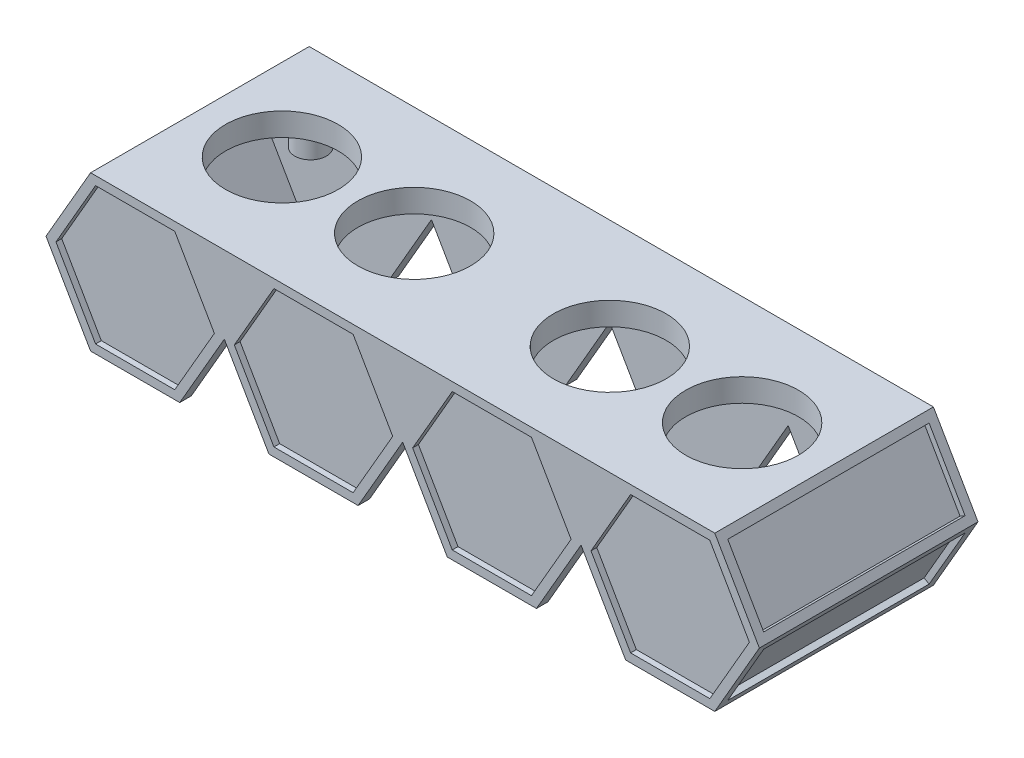
SolidWorks part; units mm, degrees
ref_plane "Front Plane" through (0, 0, 0) normal (0, 0, 1) x (1, 0, 0)
ref_plane "Top Plane" through (0, 0, 0) normal (0, 1, 0) x (1, 0, 0)
ref_plane "Right Plane" through (0, 0, 0) normal (1, 0, 0) x (0, 0, -1)
sketch "Sketch1" plane through (0, 0, 0) normal (0, 0, 1) x (1, 0, 0)
  line L0 (7.75, 13.4234) -> (23.25, 13.4234)
  line L1 (15.5, 0) -> (7.75, 13.4234)
  line L2 (7.75, 13.4234) -> (-7.75, 13.4234)
  line L3 (-7.75, 13.4234) -> (-15.5, 0)
  line L4 (-15.5, 0) -> (-7.75, -13.4234)
  line L5 (-7.75, -13.4234) -> (7.75, -13.4234)
  line L6 (7.75, -13.4234) -> (15.5, 0)
  line L7 (15.5, 0) -> (23.25, -13.4234)
  line L8 (23.25, -13.4234) -> (38.75, -13.4234)
  line L9 (38.75, -13.4234) -> (46.5, 0)
  line L10 (46.5, 0) -> (38.75, 13.4234)
  line L11 (38.75, 13.4234) -> (23.25, 13.4234)
  line L12 (23.25, 13.4234) -> (15.5, 0)
  line L13 (46.5, 0) -> (54.25, -13.4234)
  line L14 (54.25, -13.4234) -> (69.75, -13.4234)
  line L15 (69.75, -13.4234) -> (77.5, 0)
  line L16 (77.5, 0) -> (69.75, 13.4234)
  line L17 (69.75, 13.4234) -> (54.25, 13.4234)
  line L18 (54.25, 13.4234) -> (46.5, 0)
  line L19 (77.5, 0) -> (85.25, -13.4234)
  line L20 (85.25, -13.4234) -> (100.75, -13.4234)
  line L21 (100.75, -13.4234) -> (108.5, 0)
  line L22 (108.5, 0) -> (100.75, 13.4234)
  line L23 (100.75, 13.4234) -> (85.25, 13.4234)
  line L24 (85.25, 13.4234) -> (77.5, 0)
  line L25 (38.75, 13.4234) -> (54.25, 13.4234)
  line L26 (69.75, 13.4234) -> (85.25, 13.4234)
  circle A0 centre (0, 0) radius 13.4234 construction
  circle A1 centre (31, 0) radius 13.4234 construction
  circle A2 centre (62, 0) radius 13.4234 construction
  circle A3 centre (93, 0) radius 13.4234 construction
  dimension "D1" = 31
extrude "Boss-Extrude1" add sketch "Sketch1" along normal blind 38 contours L5 L6 L1 L2 L3 L4 | L12 L0 L1 | L11 L12 L7 L8 L9 L10 | L25 L10 L18 | L17 L18 L13 L14 L15 L16 | L26 L16 L24 | L23 L24 L19 L20 L21 L22 region at (15.5, 8.9489, 0) region at (0, 0, 0) region at (31, 0, 0) region at (46.5, 8.9489, 0) region at (62, 0, 0) region at (77.5, 8.9489, 0) region at (93, 0, 0)
ref_plane "Plane1" through (0, 0, 19) normal (0, 0, 1) x (1, 0, 0)
shell "Shell2" thickness 2 removed face at (0, -13.4234, 19) removed face at (11.625, -6.7117, 19) removed face at (19.375, -6.7117, 19) removed face at (31, -13.4234, 19) removed face at (42.625, -6.7117, 19) removed face at (50.375, -6.7117, 19) removed face at (62, -13.4234, 19) removed face at (73.625, -6.7117, 19) removed face at (81.375, -6.7117, 19) removed face at (93, -13.4234, 19)
sketch "Sketch3" plane through (0, 0, 38) normal (0, 0, 1) x (1, 0, 0)
  line L0 (7.75, -13.4234) -> (15.5, 0) construction
  line L1 (13.7679, 0) -> (6.884, 11.9234)
  line L2 (6.884, 11.9234) -> (-6.884, 11.9234)
  line L3 (-6.884, 11.9234) -> (-13.7679, 0)
  line L4 (-13.7679, 0) -> (-6.884, -11.9234)
  line L5 (-6.884, -11.9234) -> (6.884, -11.9234)
  line L6 (6.884, -11.9234) -> (13.7679, 0)
  line L7 (38.75, -13.4234) -> (46.5, 0) construction
  line L8 (44.7679, 0) -> (37.884, 11.9234)
  line L9 (37.884, 11.9234) -> (24.116, 11.9234)
  line L10 (24.116, 11.9234) -> (17.2321, 0)
  line L11 (17.2321, 0) -> (24.116, -11.9234)
  line L12 (24.116, -11.9234) -> (37.884, -11.9234)
  line L13 (37.884, -11.9234) -> (44.7679, 0)
  line L14 (75.7679, 0) -> (68.884, 11.9234)
  line L15 (68.884, 11.9234) -> (55.116, 11.9234)
  line L16 (55.116, 11.9234) -> (48.2321, 0)
  line L17 (48.2321, 0) -> (55.116, -11.9234)
  line L18 (55.116, -11.9234) -> (68.884, -11.9234)
  line L19 (68.884, -11.9234) -> (75.7679, 0)
  line L20 (106.7679, 0) -> (99.884, 11.9234)
  line L21 (99.884, 11.9234) -> (86.116, 11.9234)
  line L22 (86.116, 11.9234) -> (79.2321, 0)
  line L23 (79.2321, 0) -> (86.116, -11.9234)
  line L24 (86.116, -11.9234) -> (99.884, -11.9234)
  line L25 (99.884, -11.9234) -> (106.7679, 0)
  line L26 (69.75, -13.4234) -> (77.5, 0) construction
  line L27 (100.75, -13.4234) -> (108.5, 0) construction
  circle A0 centre (0, 0) radius 11.9234 construction
  circle A1 centre (31, 0) radius 11.9234 construction
  circle A2 centre (62, 0) radius 11.9234 construction
  circle A3 centre (93, 0) radius 11.9234 construction
  dimension "D1" = 1.5
  dimension "D2" = 1.5
  dimension "D3" = 1.5
  dimension "D4" = 1.5
extrude "Cut-Extrude2" cut sketch "Sketch3" against normal blind 1
extrude "Cut-Extrude3" cut sketch "Sketch3<2>" along normal blind 1 from surface starting at face at (46.5, -5.3694, 0)
sketch "Sketch3<2>" plane through (0, 0, 38) normal (0, 0, 1) x (1, 0, 0) same geometry as "Sketch3"
sketch "Sketch4" plane through (81.375, 46.9819, 0) normal (0.866, 0.5, 0) x (0, 0, -1)
  line L8 (-1.5, -52.75) -> (-1.5, -40.25)
  line L9 (-1.5, -40.25) -> (-36.5, -40.25)
  line L10 (-36.5, -40.25) -> (-36.5, -52.75)
  line L11 (-36.5, -52.75) -> (-1.5, -52.75)
  line L12 (-1.5, -52.75) -> (-1.5, -40.25)
  line L13 (-1.5, -40.25) -> (-36.5, -40.25)
  line L14 (-36.5, -40.25) -> (-36.5, -52.75)
  line L15 (-36.5, -52.75) -> (-1.5, -52.75)
  dimension "D1" = 1.5
extrude "Cut-Extrude4" cut sketch "Sketch4" against normal blind 1
sketch "Sketch5" plane through (-11.625, 6.7117, 0) normal (-0.866, 0.5, 0) x (0, 0, 1)
  line L8 (1.5, 6.25) -> (1.5, -6.25)
  line L9 (1.5, -6.25) -> (36.5, -6.25)
  line L10 (36.5, -6.25) -> (36.5, 6.25)
  line L11 (36.5, 6.25) -> (1.5, 6.25)
  line L12 (1.5, 6.25) -> (1.5, -6.25)
  line L13 (1.5, -6.25) -> (36.5, -6.25)
  line L14 (36.5, -6.25) -> (36.5, 6.25)
  line L15 (36.5, 6.25) -> (1.5, 6.25)
  dimension "D1" = 1.5
extrude "Cut-Extrude5" cut sketch "Sketch5" against normal blind 1
sketch "Sketch7" plane through (-11.625, -6.7117, 0) normal (-0.866, -0.5, 0) x (0, 0, 1)
  line L8 (1.5, 6.25) -> (1.5, -6.25)
  line L9 (1.5, -6.25) -> (36.5, -6.25)
  line L10 (36.5, -6.25) -> (36.5, 6.25)
  line L11 (36.5, 6.25) -> (1.5, 6.25)
  line L12 (1.5, 6.25) -> (1.5, -6.25)
  line L13 (1.5, -6.25) -> (36.5, -6.25)
  line L14 (36.5, -6.25) -> (36.5, 6.25)
  line L15 (36.5, 6.25) -> (1.5, 6.25)
  dimension "D1" = 1.5
extrude "Cut-Extrude7" cut sketch "Sketch7" against normal blind 1
sketch "Sketch8" plane through (81.375, -46.9819, 0) normal (0.866, -0.5, 0) x (0, 0, -1)
  line L8 (-1.5, 40.25) -> (-1.5, 52.75)
  line L9 (-1.5, 52.75) -> (-36.5, 52.75)
  line L10 (-36.5, 52.75) -> (-36.5, 40.25)
  line L11 (-36.5, 40.25) -> (-1.5, 40.25)
  line L12 (-1.5, 40.25) -> (-1.5, 52.75)
  line L13 (-1.5, 52.75) -> (-36.5, 52.75)
  line L14 (-36.5, 52.75) -> (-36.5, 40.25)
  line L15 (-36.5, 40.25) -> (-1.5, 40.25)
  dimension "D1" = 1.5
extrude "Cut-Extrude8" cut sketch "Sketch8" against normal blind 1
sketch "Sketch6" plane through (0, 13.4234, 0) normal (0, 1, 0) x (1, 0, 0)
  line L0 (-7.75, -19) -> (100.75, -19) construction
  line L1 (-7.75, -38) -> (-7.75, 0) construction
  line L2 (100.75, -38) -> (100.75, 0) construction
  line L3 (100.75, 0) -> (-7.75, 0) construction
  circle A0 centre (6.5, -19) radius 9.8
  circle A1 centre (29.5, -19) radius 9.8
  circle A2 centre (63.5, -19) radius 9.8
  circle A3 centre (86.5, -19) radius 9.8
  point P21 (46.5, 0)
  dimension "D1" = 19.6
  dimension "D2" = 23
  dimension "D3" = 23
  dimension "D4" = 34
  dimension "D5" = 17
extrude "Cut-Extrude6" cut sketch "Sketch6" against normal blind 10
sketch "Sketch9" plane through (0, 11.4234, 0) normal (0, -1, 0) x (1, 0, 0)
  line L0 (-0.5, 31) -> (-0.5, 7) construction
  line L1 (-0.5, 7) -> (93.5, 7) construction
  line L2 (93.5, 7) -> (93.5, 31) construction
  line L3 (-15.5, 38) -> (-15.5, 0) construction
  line L4 (100.75, 0) -> (-7.75, 0) construction
  circle A0 centre (-0.5, 31) radius 1.5
  circle A1 centre (-0.5, 7) radius 1.5
  circle A2 centre (-0.5, 31) radius 2.75
  circle A3 centre (-0.5, 7) radius 2.75
  circle A4 centre (93.5, 31) radius 1.5
  circle A5 centre (93.5, 31) radius 2.75
  circle A6 centre (93.5, 7) radius 1.5
  circle A7 centre (93.5, 7) radius 2.75
  point P14 (-15.5, 19)
  point P15 (-0.5, 19)
  point P18 (46.5, 0)
  point P19 (46.5, 7)
  dimension "D2" = 5.5
  dimension "D3" = 3
  dimension "D1" = 24
  dimension "D4" = 94
extrude "Boss-Extrude2" add sketch "Sketch9" along normal blind 6
sketch "Sketch11" plane through (0, 11.4234, 0) normal (0, -1, 0) x (1, 0, 0)
  line L0 (99.5953, 36) -> (-6.5953, 36) construction
  line L1 (51.1, 34.5) -> (53.1, 34.5)
  line L2 (51.1, 34.5) -> (51.1, 36)
  line L3 (51.1, 36) -> (53.1, 36)
  line L4 (53.1, 34.5) -> (53.1, 36)
  line L5 (53.1, 34.5) -> (70.9, 34.5) construction
  line L6 (72.9, 34.5) -> (70.9, 34.5)
  line L7 (72.9, 34.5) -> (72.9, 36)
  line L8 (72.9, 36) -> (70.9, 36)
  line L9 (70.9, 34.5) -> (70.9, 36)
  line L10 (54.25, 36) -> (69.75, 36) construction
  point P10 (62, 34.5)
  point P13 (62, 36)
  dimension "D1" = 17.8
  dimension "D2" = 2
  dimension "D3" = 1.5
extrude "Boss-Extrude5" add sketch "Sketch11" along normal blind 18
sketch "Sketch12" plane through (0, 11.4234, 0) normal (0, -1, 0) x (1, 0, 0)
  line L1 (53.1, 34.5) -> (70.9, 34.5)
  line L2 (53.1, 34.5) -> (53.1, 36.5)
  line L3 (53.1, 36.5) -> (70.9, 36.5)
  line L4 (70.9, 34.5) -> (70.9, 36.5)
  dimension "D1" = 0.5
extrude "Cut-Extrude9" cut sketch "Sketch12" along normal up to surface (18 mm away) up to face at (52.1, -6.5766, 35.25)
sketch "Sketch14" plane through (0, 11.4234, 0) normal (0, -1, 0) x (1, 0, 0)
  circle A0 centre (6.5, 19) radius 10.8
  circle A1 centre (29.5, 19) radius 10.8
  circle A2 centre (63.5, 19) radius 10.8
  circle A3 centre (86.5, 19) radius 10.8
  circle A4 centre (63.5, 19) radius 9.8 construction
  circle A5 centre (86.5, 19) radius 9.8 construction
  circle A6 centre (29.5, 19) radius 9.8 construction
  circle A7 centre (6.5, 19) radius 9.8 construction
  circle A8 centre (63.5, 19) radius 9.8
  circle A9 centre (86.5, 19) radius 9.8
  circle A10 centre (29.5, 19) radius 9.8
  circle A11 centre (6.5, 19) radius 9.8
  dimension "D1" = 1
extrude "Boss-Extrude6" add sketch "Sketch14" along normal blind 2
equation "\"D5@Sketch6\"=\"D4@Sketch6\"/2"
equation "\"D2@Sketch6\"=\"D3@Sketch6\""
